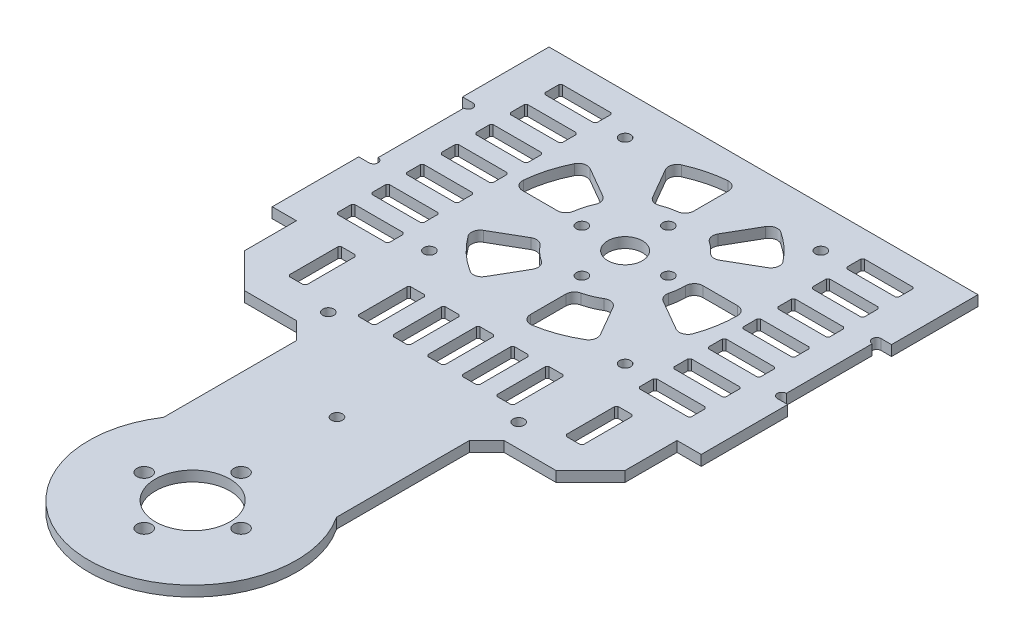
SolidWorks part; units mm, degrees
material "Thornel Mat VMA"
ref_plane "前视基准面" through (0, 0, 0) normal (0, 0, 1) x (1, 0, 0)
ref_plane "上视基准面" through (0, 0, 0) normal (0, 1, 0) x (1, 0, 0)
ref_plane "右视基准面" through (0, 0, 0) normal (1, 0, 0) x (0, 0, -1)
sketch "草图1" plane through (0, 0, 0) normal (0, 1, 0) x (1, 0, 0)
  line L0 (-52.5, 0) -> (52.5, 0) construction
  line L1 (-52.5, 0) -> (-114.5, 0) construction
  line L2 (-114.5, 40) -> (-114.5, -40)
  line L3 (-114.5, 40) -> (75.5, 40)
  line L4 (-114.5, -40) -> (75.5, -40)
  line L5 (75.5, -40) -> (75.5, 40)
  circle A0 centre (52.5, 0) radius 14 construction
  circle A1 centre (38.5, 0) radius 2.1
  circle A2 centre (52.5, 14) radius 2.1
  circle A3 centre (66.5, 0) radius 2.1
  circle A4 centre (52.5, -14) radius 2.1
  circle A5 centre (-40, 0) radius 1.6
  circle A6 centre (-52.5, -12.5) radius 1.6
  circle A7 centre (-65, 0) radius 1.6
  circle A9 centre (52.5, 0) radius 10.75
  circle A10 centre (-52.5, 0) radius 5
  circle A11 centre (-52.5, 0) radius 12.5 construction
  circle A12 centre (-52.5, 12.5) radius 1.6
  point P17 (52.5, 0)
  point P22 (50, 0)
  point P31 (-52.5, 0)
  point P35 (-51.25, 1.25)
  dimension "D2" = 28
  dimension "D3" = 4.2
  dimension "D5" = 21.5
  dimension "D6" = 10
  dimension "D7" = 25
  dimension "D8" = 3.2
  dimension "D1" = 105
  dimension "D10" = 62
  dimension "D11" = 80
  dimension "D12" = 190
  dimension "D4" = 4
  dimension "D9" = 4
extrude "凸台-拉伸1" add sketch "草图1" along normal blind 3
sketch "草图2" plane through (0, 3, 0) normal (0, 1, 0) x (1, 0, 0)
  line L0 (-52.5, 0) -> (-76.6253, 0) construction
  line L1 (-52.5, 0) -> (-52.5, 21.2161) construction
  line L2 (-52.5, 0) -> (-80.7843, 28.2843) construction
  circle A0 centre (-80.7843, 28.2843) radius 1.6
  circle A1 centre (-80.7843, -28.2843) radius 1.6
  circle A2 centre (-24.2157, -28.2843) radius 1.6
  circle A3 centre (-24.2157, 28.2843) radius 1.6
  dimension "D3" = 3.2
  dimension "D1" = 45
  dimension "D2" = 40
extrude "切除-拉伸1" cut sketch "草图2" against normal up to next
sketch "草图3" plane through (0, 3, 0) normal (0, 1, 0) x (1, 0, 0)
  line L0 (-114.5, 40) -> (-114.5, -40) construction
  line L1 (-117.5, -15) -> (-111.5, -15)
  line L2 (-117.5, -15) -> (-117.5, 15)
  line L3 (-117.5, 15) -> (-111.5, 15)
  line L4 (-111.5, -15) -> (-111.5, 15)
  line L5 (-117.5, -15) -> (-111.5, 15) construction
  line L6 (-117.5, 15) -> (-111.5, -15) construction
  point P0 (-114.5, 0)
  dimension "D1" = 6
  dimension "D2" = 30
extrude "切除-拉伸2" cut sketch "草图3" against normal up to next
sketch "草图4" plane through (0, 3, 0) normal (0, 1, 0) x (1, 0, 0)
  line L0 (-111.5, -15) -> (-111.5, 15) construction
  circle A0 centre (-111.5, 13.7) radius 1.3
  circle A1 centre (-111.5, -13.7) radius 1.3
  dimension "D1" = 2.6
  dimension "D2" = 2.6
extrude "切除-拉伸3" cut sketch "草图4" against normal up to next
sketch "草图5" plane through (0, 3, 0) normal (0, 1, 0) x (1, 0, 0)
  line L0 (-111.5, 0) -> (8, 0) construction
  line L1 (-111.5, -12.4) -> (-111.5, 12.4) construction
  line L3 (9.5, 15) -> (6.5, 15)
  line L4 (9.5, 15) -> (9.5, -15)
  line L5 (9.5, -15) -> (6.5, -15)
  line L6 (6.5, 15) -> (6.5, -15)
  line L7 (9.5, 15) -> (6.5, -15) construction
  line L8 (9.5, -15) -> (6.5, 15) construction
  dimension "D1" = 119.5
  dimension "D2" = 30
  dimension "D3" = 3
extrude "切除-拉伸4" cut sketch "草图5" against normal up to next
sketch "草图7" plane through (0, 3, 0) normal (0, 1, 0) x (1, 0, 0)
  line L0 (9.5, -15) -> (9.5, 15) construction
  line L1 (6.5, 15) -> (6.5, -15) construction
  line L2 (9.5, 0) -> (6.5, 0) construction
  circle A0 centre (9.5, 13.7) radius 1.3
  circle A1 centre (6.5, 13.7) radius 1.3
  circle A2 centre (6.5, -13.7) radius 1.3
  circle A3 centre (9.5, -13.7) radius 1.3
  dimension "D1" = 2.6
  dimension "D2" = 2.6
extrude "切除-拉伸6" cut sketch "草图7" against normal up to next
sketch "草图8" plane through (0, 3, 0) normal (0, 1, 0) x (1, 0, 0)
  line L0 (-80.7843, 28.2843) -> (-80.7843, -28.2843) construction
  line L1 (-80.7843, 0) -> (-111.5, 0) construction
  line L2 (-111.5, -12.4) -> (-111.5, 12.4) construction
  line L3 (-103.6421, 2) -> (-103.1421, 2.5)
  line L4 (-103.1421, 2.5) -> (-89.1421, 2.5)
  line L5 (-103.6421, 2) -> (-103.6421, -2)
  line L6 (-103.1421, -2.5) -> (-89.1421, -2.5)
  line L7 (-88.6421, 2) -> (-88.6421, -2)
  line L8 (-103.6421, 2.5) -> (-88.6421, -2.5) construction
  line L9 (-103.6421, -2.5) -> (-88.6421, 2.5) construction
  line L10 (-103.6421, -2) -> (-103.1421, -2.5)
  line L11 (-89.1421, 2.5) -> (-88.6421, 2)
  line L12 (-88.6421, -2) -> (-89.1421, -2.5)
  line L13 (-103.6421, 12) -> (-103.6421, 8)
  line L14 (-103.6421, 12) -> (-103.1421, 12.5)
  line L15 (-103.1421, 12.5) -> (-89.1421, 12.5)
  line L16 (-89.1421, 12.5) -> (-88.6421, 12)
  line L17 (-88.6421, 12) -> (-88.6421, 8)
  line L18 (-88.6421, 8) -> (-89.1421, 7.5)
  line L19 (-103.1421, 7.5) -> (-89.1421, 7.5)
  line L20 (-103.6421, 8) -> (-103.1421, 7.5)
  line L21 (-103.6421, 22) -> (-103.6421, 18)
  line L22 (-103.6421, 22) -> (-103.1421, 22.5)
  line L23 (-103.1421, 22.5) -> (-89.1421, 22.5)
  line L24 (-89.1421, 22.5) -> (-88.6421, 22)
  line L25 (-88.6421, 22) -> (-88.6421, 18)
  line L26 (-88.6421, 18) -> (-89.1421, 17.5)
  line L27 (-103.1421, 17.5) -> (-89.1421, 17.5)
  line L28 (-103.6421, 18) -> (-103.1421, 17.5)
  line L29 (-103.6421, 32) -> (-103.6421, 28)
  line L30 (-103.6421, 32) -> (-103.1421, 32.5)
  line L31 (-103.1421, 32.5) -> (-89.1421, 32.5)
  line L32 (-89.1421, 32.5) -> (-88.6421, 32)
  line L33 (-88.6421, 32) -> (-88.6421, 28)
  line L34 (-88.6421, 28) -> (-89.1421, 27.5)
  line L35 (-103.1421, 27.5) -> (-89.1421, 27.5)
  line L36 (-103.6421, 28) -> (-103.1421, 27.5)
  line L37 (-103.6421, -28) -> (-103.1421, -27.5)
  line L38 (-103.1421, -27.5) -> (-89.1421, -27.5)
  line L39 (-88.6421, -28) -> (-89.1421, -27.5)
  line L40 (-88.6421, -32) -> (-88.6421, -28)
  line L41 (-89.1421, -32.5) -> (-88.6421, -32)
  line L42 (-103.6421, -32) -> (-103.1421, -32.5)
  line L43 (-103.6421, -32) -> (-103.6421, -28)
  line L44 (-103.6421, -18) -> (-103.1421, -17.5)
  line L45 (-103.1421, -17.5) -> (-89.1421, -17.5)
  line L46 (-88.6421, -18) -> (-89.1421, -17.5)
  line L47 (-88.6421, -22) -> (-88.6421, -18)
  line L48 (-89.1421, -22.5) -> (-88.6421, -22)
  line L49 (-103.1421, -22.5) -> (-89.1421, -22.5)
  line L50 (-103.6421, -22) -> (-103.1421, -22.5)
  line L51 (-103.6421, -22) -> (-103.6421, -18)
  line L52 (-103.6421, -8) -> (-103.1421, -7.5)
  line L53 (-103.1421, -7.5) -> (-89.1421, -7.5)
  line L54 (-88.6421, -8) -> (-89.1421, -7.5)
  line L55 (-88.6421, -12) -> (-88.6421, -8)
  line L56 (-89.1421, -12.5) -> (-88.6421, -12)
  line L57 (-103.1421, -12.5) -> (-89.1421, -12.5)
  line L58 (-103.6421, -12) -> (-103.1421, -12.5)
  line L59 (-103.6421, -12) -> (-103.6421, -8)
  line L60 (-103.1421, -32.5) -> (-89.1421, -32.5)
  line L61 (-52.5, 0) -> (-52.5, -34.4819) construction
  line L62 (-1.3579, -2.5) -> (-16.3579, 2.5) construction
  line L63 (-1.3579, 2.5) -> (-16.3579, -2.5) construction
  line L64 (-24.2157, 0) -> (6.5, 0) construction
  line L65 (-1.8579, -32.5) -> (-15.8579, -32.5)
  line L66 (-1.3579, -12) -> (-1.3579, -8)
  line L67 (-1.3579, -12) -> (-1.8579, -12.5)
  line L68 (-1.8579, -12.5) -> (-15.8579, -12.5)
  line L69 (-15.8579, -12.5) -> (-16.3579, -12)
  line L70 (-16.3579, -12) -> (-16.3579, -8)
  line L71 (-16.3579, -8) -> (-15.8579, -7.5)
  line L72 (-1.8579, -7.5) -> (-15.8579, -7.5)
  line L73 (-1.3579, -8) -> (-1.8579, -7.5)
  line L74 (-1.3579, -22) -> (-1.3579, -18)
  line L75 (-1.3579, -22) -> (-1.8579, -22.5)
  line L76 (-1.8579, -22.5) -> (-15.8579, -22.5)
  line L77 (-15.8579, -22.5) -> (-16.3579, -22)
  line L78 (-16.3579, -22) -> (-16.3579, -18)
  line L79 (-16.3579, -18) -> (-15.8579, -17.5)
  line L80 (-1.8579, -17.5) -> (-15.8579, -17.5)
  line L81 (-1.3579, -18) -> (-1.8579, -17.5)
  line L82 (-1.3579, -32) -> (-1.3579, -28)
  line L83 (-1.3579, -32) -> (-1.8579, -32.5)
  line L84 (-15.8579, -32.5) -> (-16.3579, -32)
  line L85 (-16.3579, -32) -> (-16.3579, -28)
  line L86 (-16.3579, -28) -> (-15.8579, -27.5)
  line L87 (-1.8579, -27.5) -> (-15.8579, -27.5)
  line L88 (-1.3579, -28) -> (-1.8579, -27.5)
  line L89 (-1.3579, 28) -> (-1.8579, 27.5)
  line L90 (-1.8579, 27.5) -> (-15.8579, 27.5)
  line L91 (-16.3579, 28) -> (-15.8579, 27.5)
  line L92 (-16.3579, 32) -> (-16.3579, 28)
  line L93 (-15.8579, 32.5) -> (-16.3579, 32)
  line L94 (-1.8579, 32.5) -> (-15.8579, 32.5)
  line L95 (-1.3579, 32) -> (-1.8579, 32.5)
  line L96 (-1.3579, 32) -> (-1.3579, 28)
  line L97 (-1.3579, 18) -> (-1.8579, 17.5)
  line L98 (-1.8579, 17.5) -> (-15.8579, 17.5)
  line L99 (-16.3579, 18) -> (-15.8579, 17.5)
  line L100 (-16.3579, 22) -> (-16.3579, 18)
  line L101 (-15.8579, 22.5) -> (-16.3579, 22)
  line L102 (-1.8579, 22.5) -> (-15.8579, 22.5)
  line L103 (-1.3579, 22) -> (-1.8579, 22.5)
  line L104 (-1.3579, 22) -> (-1.3579, 18)
  line L105 (-1.3579, 8) -> (-1.8579, 7.5)
  line L106 (-1.8579, 7.5) -> (-15.8579, 7.5)
  line L107 (-16.3579, 8) -> (-15.8579, 7.5)
  line L108 (-16.3579, 12) -> (-16.3579, 8)
  line L109 (-15.8579, 12.5) -> (-16.3579, 12)
  line L110 (-1.8579, 12.5) -> (-15.8579, 12.5)
  line L111 (-1.3579, 12) -> (-1.8579, 12.5)
  line L112 (-1.3579, 12) -> (-1.3579, 8)
  line L113 (-16.3579, -2) -> (-15.8579, -2.5)
  line L114 (-15.8579, 2.5) -> (-16.3579, 2)
  line L115 (-1.3579, -2) -> (-1.8579, -2.5)
  line L116 (-16.3579, 2) -> (-16.3579, -2)
  line L117 (-1.8579, -2.5) -> (-15.8579, -2.5)
  line L118 (-1.3579, 2) -> (-1.3579, -2)
  line L119 (-1.8579, 2.5) -> (-15.8579, 2.5)
  line L120 (-1.3579, 2) -> (-1.8579, 2.5)
  point P8 (-96.1421, 0)
  point P134 (-8.8579, 0)
  dimension "D1" = 15
  dimension "D2" = 5
  dimension "D3" = 4
extrude "切除-拉伸7" cut sketch "草图8" against normal up to next
sketch "草图9" plane through (0, 3, 0) normal (0, 1, 0) x (1, 0, 0)
  line L0 (-52.5, 19.8431) -> (-52.5, 29.8957)
  line L1 (-43.2569, 17.6772) -> (-38.2453, 26.3576)
  line L2 (-36.4494, 11.2864) -> (-27.6556, 16.3634)
  line L3 (-32.5, 2.5) -> (-22.5, 2.5)
  line L4 (-34.3764, -7.1314) -> (-25.4984, -12.2571)
  line L5 (-40.0737, -15.917) -> (-35.0733, -24.578)
  line L6 (-50.2263, -19.4219) -> (-50.2263, -29.6178)
  line L7 (-61.2391, -18.016) -> (-66.2437, -26.6844)
  line L8 (-69.3589, -10.3394) -> (-78.086, -15.378)
  line L9 (-72.3133, 0.2263) -> (-82.3759, 0.2263)
  line L10 (-69.4371, 10.4855) -> (-78.1232, 15.5004)
  line L11 (-61.9263, 17.3853) -> (-66.965, 26.1126)
  arc A0 (-66.1578, -10.9414) -> (-62.0411, -14.6703) centre (-52.5, 0) ccw
  arc A1 (-78.864, -19.005) -> (-69.7345, -27.554) centre (-52.5, 0) ccw
  arc A2 (-68.4137, 7.2803) -> (-69.8366, 2.3855) centre (-52.5, 0) ccw
  arc A3 (-81.6126, 14.4466) -> (-84.8655, 2.9535) centre (-52.5, 0) ccw
  arc A4 (-54.6875, 17.3627) -> (-58.8535, 16.3059) centre (-52.5, 0) ccw
  arc A5 (-55.2083, 32.387) -> (-65.8249, 29.6428) centre (-52.5, 0) ccw
  arc A6 (-39.5494, 11.77) -> (-42.5179, 14.3738) centre (-52.5, 0) ccw
  arc A7 (-26.9394, 20.0725) -> (-34.7119, 27.1999) centre (-52.5, 0) ccw
  arc A8 (-35.5481, -4.3456) -> (-35, 0) centre (-52.5, 0) ccw
  arc A9 (-21.8942, -10.9331) -> (-20, 0) centre (-52.5, 0) ccw
  arc A10 (-47.3285, -32.0859) -> (-35.9666, -27.9803) centre (-52.5, 0) ccw
  arc A11 (-48.323, -16.9942) -> (-43.5214, -15.0212) centre (-52.5, 0) ccw
  arc A12 (-21.8942, -10.9331) -> (-25.4984, -12.2571) centre (-24.2484, -10.0921) cw
  arc A13 (-34.3764, -7.1314) -> (-35.5481, -4.3456) centre (-33.1264, -4.9664) cw
  arc A14 (-32.5, 2.5) -> (-35, 0) centre (-32.5, 0) ccw
  arc A15 (-38.2453, 26.3576) -> (-34.7119, 27.1999) centre (-36.0803, 25.1076) cw
  arc A16 (-26.9394, 20.0725) -> (-27.6556, 16.3634) centre (-28.9056, 18.5285) cw
  arc A17 (-36.4494, 11.2864) -> (-39.5494, 11.77) centre (-37.6994, 13.4514) cw
  arc A18 (-42.5179, 14.3738) -> (-43.2569, 17.6772) centre (-41.0919, 16.4272) cw
  arc A19 (-52.5, 19.8431) -> (-54.6875, 17.3627) centre (-55, 19.8431) cw
  arc A20 (-58.8535, 16.3059) -> (-61.9263, 17.3853) centre (-59.7612, 18.6353) cw
  arc A21 (-52.5, 29.8957) -> (-55.2083, 32.387) centre (-55, 29.8957) ccw
  arc A22 (-65.8249, 29.6428) -> (-66.965, 26.1126) centre (-64.7999, 27.3626) ccw
  arc A23 (-69.8366, 2.3855) -> (-72.3133, 0.2263) centre (-72.3133, 2.7263) cw
  arc A24 (-68.4137, 7.2803) -> (-69.4371, 10.4855) centre (-70.6871, 8.3204) ccw
  arc A25 (-78.1232, 15.5004) -> (-81.6126, 14.4466) centre (-79.3732, 13.3353) ccw
  arc A26 (-82.3759, 0.2263) -> (-84.8655, 2.9535) centre (-82.3759, 2.7263) cw
  arc A27 (-61.2391, -18.016) -> (-62.0411, -14.6703) centre (-63.4041, -16.766) ccw
  arc A28 (-66.1578, -10.9414) -> (-69.3589, -10.3394) centre (-68.1089, -12.5045) ccw
  arc A29 (-66.2437, -26.6844) -> (-69.7345, -27.554) centre (-68.4088, -25.4344) cw
  arc A30 (-78.864, -19.005) -> (-78.086, -15.378) centre (-76.836, -17.543) cw
  arc A31 (-35.0733, -24.578) -> (-35.9666, -27.9803) centre (-37.2384, -25.828) cw
  arc A32 (-47.3285, -32.0859) -> (-50.2263, -29.6178) centre (-47.7263, -29.6178) cw
  arc A33 (-40.0737, -15.917) -> (-43.5214, -15.0212) centre (-42.2388, -17.167) ccw
  arc A34 (-50.2263, -19.4219) -> (-48.323, -16.9942) centre (-47.7263, -19.4219) cw
  arc A35 (-20, 0) -> (-22.5, 2.5) centre (-22.5, 0) ccw
  point P31 (-51.3632, 1.3632)
  point P43 (-52.5, 17.5)
  point P48 (-52.5, 32.5)
  dimension "D1" = 35
  dimension "D2" = 65
  dimension "D4" = 2.5
  dimension "D5" = 2.5
  dimension "D3" = 12
extrude "切除-拉伸8" cut sketch "草图9" against normal up to next
sketch "草图10" plane through (0, 3, 0) normal (0, 1, 0) x (1, 0, 0)
  line L0 (29.5, 40) -> (75.5, 8.5372)
  line L1 (75.5, 40) -> (-114.5, 40) construction
  line L2 (75.5, -40) -> (75.5, 40) construction
  line L3 (75.5, 8.5372) -> (75.5, -12.7896)
  line L4 (75.5, -12.7896) -> (29.5, -40)
  line L5 (-114.5, -40) -> (75.5, -40) construction
  arc A0 (29.5, -40) -> (29.5, 40) centre (52.5, 0) ccw
extrude "凸台-拉伸2" add sketch "草图10" against normal up to surface (3 mm away) up to face at (-43.8219, 0, 22.7663)
sketch "草图14" plane through (0, 0, 0) normal (0, -1, 0) x (1, 0, 0)
  line L0 (9.5, 0) -> (9.5, -55.7871)
  line L1 (9.5, -12.4) -> (9.5, 12.4) construction
  line L2 (9.5, -55.7871) -> (108.7563, -55.7871)
  line L3 (108.7563, -55.7871) -> (108.7563, 62.2798)
  line L4 (108.7563, 62.2798) -> (9.5, 62.2798)
  line L5 (9.5, 62.2798) -> (9.5, 0)
extrude "切除-拉伸9" cut sketch "草图14" against normal up to next
sketch "草图15" plane through (0, 0, 0) normal (0, -1, 0) x (1, 0, 0)
  line L0 (-52.5, 0) -> (-52.5, 125) construction
  line L1 (-77.5, 40) -> (-77.5, 108.4169)
  line L2 (-114.5, 40) -> (9.5, 40) construction
  line L3 (-27.5, 40) -> (-27.5, 108.4169)
  line L4 (-27.5, 40) -> (-77.5, 40)
  circle A0 centre (-52.5, 125) radius 10.75
  circle A1 centre (-52.5, 125) radius 14 construction
  circle A2 centre (-66.5, 125) radius 2.1
  circle A3 centre (-52.5, 139) radius 2.1
  circle A4 centre (-38.5, 125) radius 2.1
  circle A5 centre (-52.5, 111) radius 2.1
  arc A6 (-27.5, 108.4169) -> (-77.5, 108.4169) centre (-52.5, 125) ccw
  point P16 (-52.5, 150)
  point P23 (-52.5, 120)
  point P24 (-52.5, 125)
  dimension "D2" = 21.5
  dimension "D3" = 28
  dimension "D4" = 4.2
  dimension "D6" = 60
  dimension "D1" = 125
  dimension "D7" = 25
  dimension "D5" = 4
extrude "凸台-拉伸3" add sketch "草图15" against normal up to surface (3 mm away) up to face at (-52.5, 3, 0)
sketch "草图16" plane through (0, 0, 0) normal (0, -1, 0) x (1, 0, 0)
  line L0 (-27.5, 40) -> (2.5, 40)
  line L1 (-27.5, 40) -> (9.5, 40) construction
  line L2 (2.5, 40) -> (-27.5, 65)
  line L3 (-27.5, 40) -> (-27.5, 108.4169) construction
  line L4 (-27.5, 65) -> (-27.5, 40)
  line L5 (2.5, 40) -> (-27.5, 40)
  line L6 (-52.5, 125) -> (-52.5, 0) construction
  line L7 (-77.5, 40) -> (-107.5, 40)
  line L8 (-107.5, 40) -> (-77.5, 65)
  line L9 (-77.5, 65) -> (-77.5, 40)
  dimension "D1" = 30
  dimension "D2" = 25
extrude "凸台-拉伸4" add sketch "草图16" against normal up to surface (3 mm away) contours L2 L4 L0 | L9 L8 L7 region at (-17.5, 0, 48.3333) region at (-87.5, 0, 48.3333) up to face at (-54.35, 3, 17.1708)
sketch "草图18" plane through (0, 0, 0) normal (0, -1, 0) x (1, 0, 0)
  line L0 (-27.5, 65) -> (2.5, 65)
  line L1 (2.5, 65) -> (2.5, 40)
  line L2 (2.5, 40) -> (-27.5, 65)
  line L3 (-52.5, 125) -> (-52.5, 65) construction
  line L4 (-77.5, 65) -> (-107.5, 65)
  line L5 (-107.5, 40) -> (-77.5, 65)
  line L6 (-107.5, 65) -> (-107.5, 40)
extrude "凸台-拉伸5" add sketch "草图18" against normal up to surface (3 mm away) up to face at (-52.8182, 3, 21.5189)
sketch "草图17" plane through (0, 0, 0) normal (0, -1, 0) x (1, 0, 0)
  line L0 (-24.2157, 28.2843) -> (-80.7843, 28.2843) construction
  line L1 (-52.5, 28.2843) -> (-52.5, 58.2843) construction
  line L2 (-25, 58.2843) -> (-80, 58.2843) construction
  circle A0 centre (-25, 58.2843) radius 1.6
  circle A1 centre (-80, 58.2843) radius 1.6
  dimension "D3" = 3.2
  dimension "D4" = 3.2
  dimension "D1" = 55
  dimension "D2" = 30
extrude "切除-拉伸10" cut sketch "草图17" against normal up to next
sketch "草图19" plane through (0, 0, 0) normal (0, -1, 0) x (1, 0, 0)
  line L0 (-24.2157, 28.2843) -> (-80.7843, 28.2843) construction
  line L1 (-52.5, 28.2843) -> (-52.5, 83.2843) construction
  circle A0 centre (-52.5, 83.2843) radius 1.6
  dimension "D2" = 3.2
  dimension "D1" = 55
extrude "切除-拉伸11" cut sketch "草图19" against normal up to next
chamfer "倒角1" distance 10 angle 45 2 edges at (-107.5, 1.5, 65) (2.5, 1.5, 65)
chamfer "倒角2" distance 5 angle 45 2 edges at (-77.5, 1.5, 65) (-27.5, 1.5, 65)
sketch "草图20" plane through (0, 0, 0) normal (0, -1, 0) x (1, 0, 0)
  line L0 (2.5, 47.5) -> (-107.5, 47.5) construction
  line L1 (2.5, 40) -> (2.5, 55) construction
  line L2 (-107.5, 55) -> (-107.5, 40) construction
  line L3 (-50, 54.5) -> (-50.5, 55)
  line L4 (-50.5, 40) -> (-54.5, 40)
  line L5 (-50, 40.5) -> (-50, 54.5)
  line L6 (-50.5, 55) -> (-54.5, 55)
  line L7 (-55, 40.5) -> (-55, 54.5)
  line L8 (-50, 40) -> (-55, 55) construction
  line L9 (-50, 55) -> (-55, 40) construction
  line L10 (-54.5, 55) -> (-55, 54.5)
  line L11 (-50.5, 40) -> (-50, 40.5)
  line L12 (-54.5, 40) -> (-55, 40.5)
  line L13 (-40, 40.5) -> (-40, 54.5)
  line L14 (-40, 54.5) -> (-40.5, 55)
  line L15 (-40.5, 55) -> (-44.5, 55)
  line L16 (-44.5, 55) -> (-45, 54.5)
  line L17 (-45, 40.5) -> (-45, 54.5)
  line L18 (-44.5, 40) -> (-45, 40.5)
  line L19 (-40.5, 40) -> (-44.5, 40)
  line L20 (-40.5, 40) -> (-40, 40.5)
  line L21 (-30, 40.5) -> (-30, 54.5)
  line L22 (-30, 54.5) -> (-30.5, 55)
  line L23 (-30.5, 55) -> (-34.5, 55)
  line L24 (-34.5, 55) -> (-35, 54.5)
  line L25 (-35, 40.5) -> (-35, 54.5)
  line L26 (-34.5, 40) -> (-35, 40.5)
  line L27 (-30.5, 40) -> (-34.5, 40)
  line L28 (-30.5, 40) -> (-30, 40.5)
  line L29 (-10, 40.5) -> (-10, 54.5)
  line L30 (-15, 40.5) -> (-15, 54.5)
  line L31 (-10.5, 55) -> (-14.5, 55)
  line L32 (-10.5, 40) -> (-14.5, 40)
  line L33 (-10.5, 40) -> (-10, 40.5)
  line L34 (-14.5, 40) -> (-15, 40.5)
  line L35 (-10, 54.5) -> (-10.5, 55)
  line L36 (-14.5, 55) -> (-15, 54.5)
  line L37 (-52.5, 47.5) -> (-52.5, 72.0791) construction
  line L38 (-64.5, 40) -> (-65, 40.5)
  line L39 (-64.5, 40) -> (-60.5, 40)
  line L40 (-60.5, 40) -> (-60, 40.5)
  line L41 (-60, 40.5) -> (-60, 54.5)
  line L42 (-60.5, 55) -> (-60, 54.5)
  line L43 (-64.5, 55) -> (-60.5, 55)
  line L44 (-65, 54.5) -> (-64.5, 55)
  line L45 (-65, 40.5) -> (-65, 54.5)
  line L46 (-75, 54.5) -> (-74.5, 55)
  line L47 (-74.5, 55) -> (-70.5, 55)
  line L48 (-70.5, 55) -> (-70, 54.5)
  line L49 (-70, 40.5) -> (-70, 54.5)
  line L50 (-70.5, 40) -> (-70, 40.5)
  line L51 (-74.5, 40) -> (-70.5, 40)
  line L52 (-75, 40.5) -> (-75, 54.5)
  line L53 (-74.5, 40) -> (-75, 40.5)
  line L54 (-95, 54.5) -> (-94.5, 55)
  line L55 (-94.5, 55) -> (-90.5, 55)
  line L56 (-90.5, 55) -> (-90, 54.5)
  line L57 (-90, 40.5) -> (-90, 54.5)
  line L58 (-90.5, 40) -> (-90, 40.5)
  line L59 (-94.5, 40) -> (-90.5, 40)
  line L60 (-94.5, 40) -> (-95, 40.5)
  line L61 (-95, 40.5) -> (-95, 54.5)
  point P6 (-52.5, 47.5)
  dimension "D1" = 15
  dimension "D2" = 5
  dimension "D3" = 3
  dimension "D4" = 2
extrude "切除-拉伸12" cut sketch "草图20" against normal up to next
